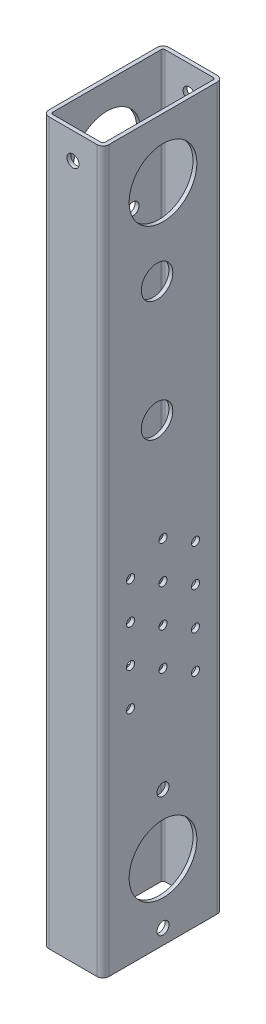
SolidWorks part; units mm, degrees
material "6061-T6 (SS)"
ref_plane "Front Plane" through (0, 0, 0) normal (0, 0, 1) x (1, 0, 0)
ref_plane "Top Plane" through (0, 0, 0) normal (0, 1, 0) x (1, 0, 0)
ref_plane "Right Plane" through (0, 0, 0) normal (1, 0, 0) x (0, 0, -1)
sketch "Sketch1" plane through (0, 0, 0) normal (0, 1, 0) x (1, 0, 0)
  line L1 (10.16, -25.4) -> (-10.16, -25.4)
  line L2 (12.7, -22.86) -> (12.7, 22.86)
  line L3 (10.16, 25.4) -> (-10.16, 25.4)
  line L4 (-12.7, -22.86) -> (-12.7, 22.86)
  line L5 (12.7, -25.4) -> (-12.7, 25.4) construction
  line L6 (12.7, 25.4) -> (-12.7, -25.4) construction
  arc A0 (-10.16, -25.4) -> (-12.7, -22.86) centre (-10.16, -22.86) cw
  arc A1 (10.16, -25.4) -> (12.7, -22.86) centre (10.16, -22.86) ccw
  arc A2 (12.7, 22.86) -> (10.16, 25.4) centre (10.16, 22.86) ccw
  arc A3 (-10.16, 25.4) -> (-12.7, 22.86) centre (-10.16, 22.86) ccw
  point P0 (0, 0)
  dimension "D3" = 2.54
  dimension "D1" = 25.4
  dimension "D2" = 50.8
extrude "Extrude-Thin1" add sketch "Sketch1" along normal blind 222.25 and the other way blind 82.55 thin thin type one direction reverse wall 1.651
sketch "Sketch2" plane through (-12.7, 0, 0) normal (-1, 0, 0) x (0, 0, 1)
  line L0 (2.54, 161.9426) -> (2.54, 12.7) construction
  line L4 (9.2075, 161.9426) -> (9.2075, 12.7)
  line L5 (-4.1275, 161.9426) -> (-4.1275, 12.7)
  line L6 (2.54, 25.4) -> (2.54, 149.2426) construction
  arc A2 (9.2075, 161.9426) -> (-4.1275, 161.9426) centre (2.54, 161.9426) ccw
  arc A3 (-4.1275, 12.7) -> (9.2075, 12.7) centre (2.54, 12.7) ccw
  point P3 (2.54, 87.3213)
  dimension "D5" = 13.335
  dimension "D2" = 12.7
  dimension "D1" = 12.7
extrude "Cut-Extrude1" cut sketch "Sketch2" against normal up to next
sketch "Sketch5" plane through (12.7, 0, 0) normal (1, 0, 0) x (0, 0, -1)
  circle A3 centre (-2.54, 111.1426) radius 6.6675 construction
  circle A4 centre (-2.54, 111.1426) radius 6.6675
  circle A5 centre (-2.54, 161.9426) radius 6.6675 construction
  circle A6 centre (-2.54, 161.9426) radius 6.6675
extrude "Cut-Extrude4" cut sketch "Sketch5" against normal up to next
sketch "Sketch4" plane through (-12.7, 0, 0) normal (1, 0, 0) x (0, 0, -1)
  circle A12 centre (11.049, 4.7713) radius 2.5527
  circle A13 centre (-16.129, 4.7713) radius 2.5527
  circle A14 centre (-16.129, 87.3213) radius 2.5527
  circle A15 centre (11.049, 87.3213) radius 2.5527
  circle A16 centre (-16.129, 169.8713) radius 2.5527
  circle A17 centre (11.049, 169.8713) radius 2.5527
  dimension "D1" = 5.1054
extrude "Cut-Extrude3" cut sketch "Sketch4" along normal up to surface (1.651 mm away) up to face at (-11.049, 87.3213, 2.54)
sketch "Sketch6" plane through (12.7, 0, 0) normal (1, 0, 0) x (0, 0, -1)
  line L0 (25.4, -82.55) -> (25.4, 222.25) construction
  circle A0 centre (0, -50.8) radius 14.3256
  circle A1 centre (0, 196.85) radius 14.3256
  dimension "D1" = 28.6512
  dimension "D2" = 25.4
  dimension "D3" = 50.8
  dimension "D4" = 247.65
extrude "Cut-Extrude5" cut sketch "Sketch6" against normal through all
hole_wizard "#10 Clearance Hole1" positions "Sketch8" profile "Sketch9" hole size "#10" standard "ANSI Inch" end condition through all
sketch "Sketch8" plane through (12.7, 0, 0) normal (1, 0, 0) x (0, 0, -1)
  circle A0 centre (0, -50.8) radius 25.4 construction
  point P0 (0, -25.4)
  point P11 (0, -76.2)
  dimension "D1" = 50.8
sketch "Sketch9" plane through (12.7, -25.4, 0) normal (0, 1, 0) x (0, 0, -1)
  line L0 (0, 0) -> (0, 25.4)
  line L1 (0, 25.4) -> (2.5527, 25.4)
  line L2 (2.5527, 25.4) -> (2.5527, 0)
  line L5 (2.5527, 0) -> (0, 0)
  line L11 (0, -6.35) -> (0, 107.95) construction
  dimension "Thru Hole Dia." = 5.1054
  dimension "Thru Hole Depth" = 25.4
hole_wizard "1/8 (0.135) Diameter Hole1" positions "Sketch10" profile "Sketch11" hole size "1/8" standard "ANSI Inch" end condition up to next
sketch "Sketch10" plane through (12.7, 0, 0) normal (1, 0, 0) x (0, 0, -1)
  point P0 (0, 66.5303)
  point P3 (13.7482, 58.5928)
  point P8 (-13.7482, 58.5928)
  point P11 (-13.7482, 42.7178)
  point P14 (13.7482, 42.7178)
  point P17 (0, 34.7803)
  point P20 (-13.7482, 26.8428)
  point P23 (13.7482, 26.8428)
  point P26 (0, 18.9053)
  point P29 (13.7482, 10.9678)
  point P32 (-13.7482, 10.9678)
  point P35 (0, 50.6553)
sketch "Sketch11" plane through (12.7, 66.5303, 0) normal (0, 1, 0) x (0, 0, -1)
  line L0 (0, 0) -> (0, 1.651)
  line L1 (0, 1.651) -> (1.7145, 1.651)
  line L2 (1.7145, 1.651) -> (1.7145, 0)
  line L5 (1.7145, 0) -> (0, 0)
  line L11 (0, -6.35) -> (0, 107.95) construction
  dimension "Thru Hole Dia." = 3.429
  dimension "Thru Hole Depth" = 1.651
hole_wizard "1/8 (0.135) Diameter Hole2" positions "Sketch12" profile "Sketch13" hole size "1/8" standard "ANSI Inch" end condition up to next
sketch "Sketch12" plane through (-12.7, 0, 0) normal (-1, 0, 0) x (0, 0, 1)
  point P0 (17.399, 63.3553)
  point P3 (17.399, 53.8303)
  point P6 (17.399, 44.3053)
  point P9 (17.399, 34.7803)
  point P12 (17.399, 25.2553)
  point P15 (17.399, 15.7303)
sketch "Sketch13" plane through (-12.7, 63.3553, 17.399) normal (0, 1, 0) x (0, 0, 1)
  line L0 (0, 0) -> (0, 1.651)
  line L1 (0, 1.651) -> (1.7145, 1.651)
  line L2 (1.7145, 1.651) -> (1.7145, 0)
  line L5 (1.7145, 0) -> (0, 0)
  line L11 (0, -6.35) -> (0, 107.95) construction
  dimension "Thru Hole Dia." = 3.429
  dimension "Thru Hole Depth" = 1.651
hole_wizard "#10 Clearance Hole2" positions "Sketch14" profile "Sketch15" hole size "#10" standard "ANSI Inch" end condition through all
sketch "Sketch14" plane through (0, 0, -25.4) normal (0, 0, -1) x (-1, 0, 0)
  point P0 (0, 211.1375)
sketch "Sketch15" plane through (0, 211.1375, -25.4) normal (1, 0, 0) x (0, 1, 0)
  line L0 (0, 0) -> (0, 50.8)
  line L1 (0, 50.8) -> (2.5527, 50.8)
  line L2 (2.5527, 50.8) -> (2.5527, 0)
  line L5 (2.5527, 0) -> (0, 0)
  line L11 (0, -6.35) -> (0, 107.95) construction
  dimension "Thru Hole Dia." = 5.1054
  dimension "Thru Hole Depth" = 50.8
move or copy body "Body-Move/Copy1" [suppressed] bodies to move or copy 110 parameters "D1"=0, "D2"=0, "D3"=0
